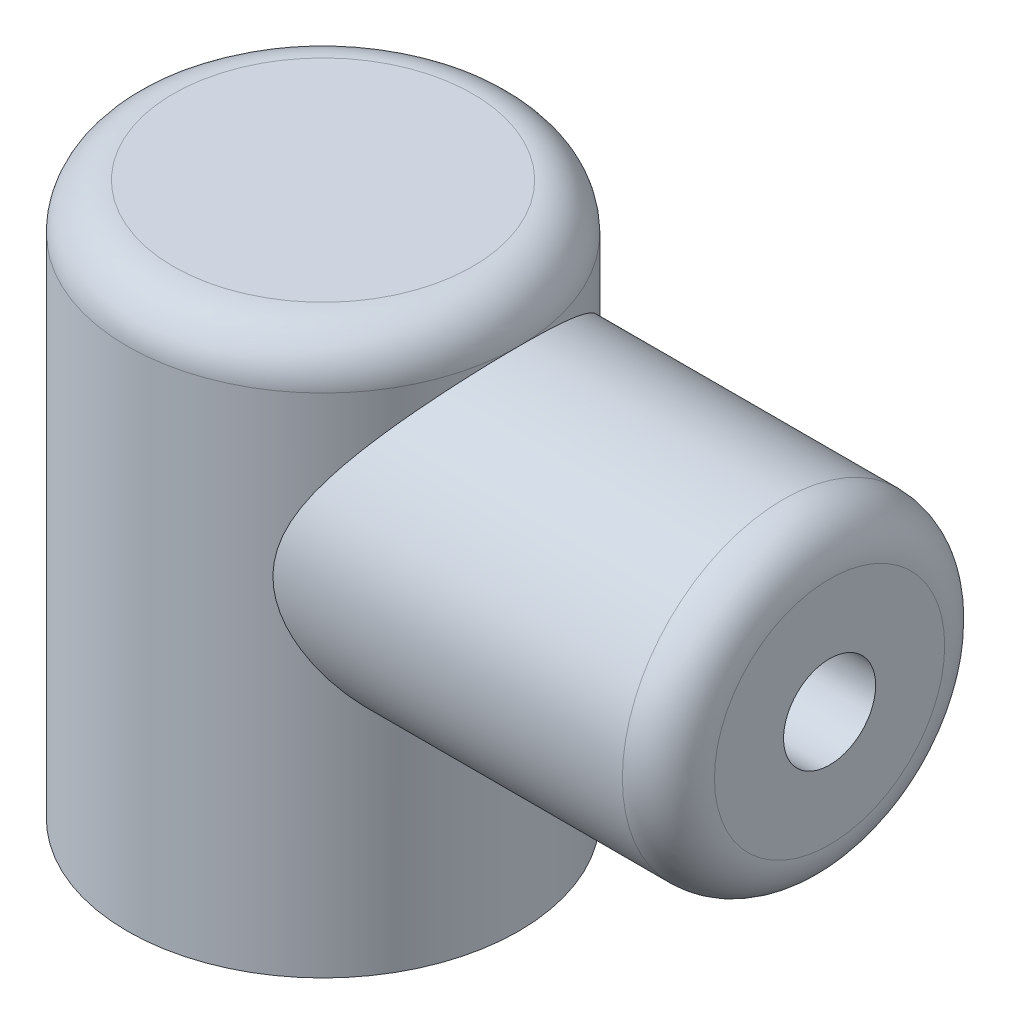
SolidWorks part; units mm, degrees
ref_plane "Front Plane" through (0, 0, 0) normal (0, 0, 1) x (1, 0, 0)
ref_plane "Top Plane" through (0, 0, 0) normal (0, 1, 0) x (1, 0, 0)
ref_plane "Right Plane" through (0, 0, 0) normal (1, 0, 0) x (0, 0, -1)
sketch "Sketch1" plane through (0, 0, 0) normal (0, 1, 0) x (1, 0, 0)
  circle A0 centre (0, 0) radius 42.5
  dimension "D1" = 85
extrude "Boss-Extrude1" add sketch "Sketch1" along normal blind 120
sketch "Sketch2" plane through (0, 0, 0) normal (1, 0, 0) x (0, 0, -1)
  line L0 (0, 120) -> (0, 75) construction
  line L1 (42.5, 120) -> (-42.5, 120) construction
  circle A0 centre (0, 75) radius 35
  dimension "D2" = 70
  dimension "D1" = 45
extrude "Boss-Extrude2" add sketch "Sketch2" along normal blind 110
fillet "Fillet1" radius 10 1 edges at (0, 120, 42.5)
sketch "Sketch3" plane through (110, 0, 0) normal (1, 0, 0) x (0, 0, -1)
  circle A0 centre (0, 75) radius 10
  dimension "D1" = 20
extrude "Cut-Extrude1" cut sketch "Sketch3" against normal blind 40 contours A0
fillet "Fillet2" radius 10 1 edges at (110, 75, -35)
